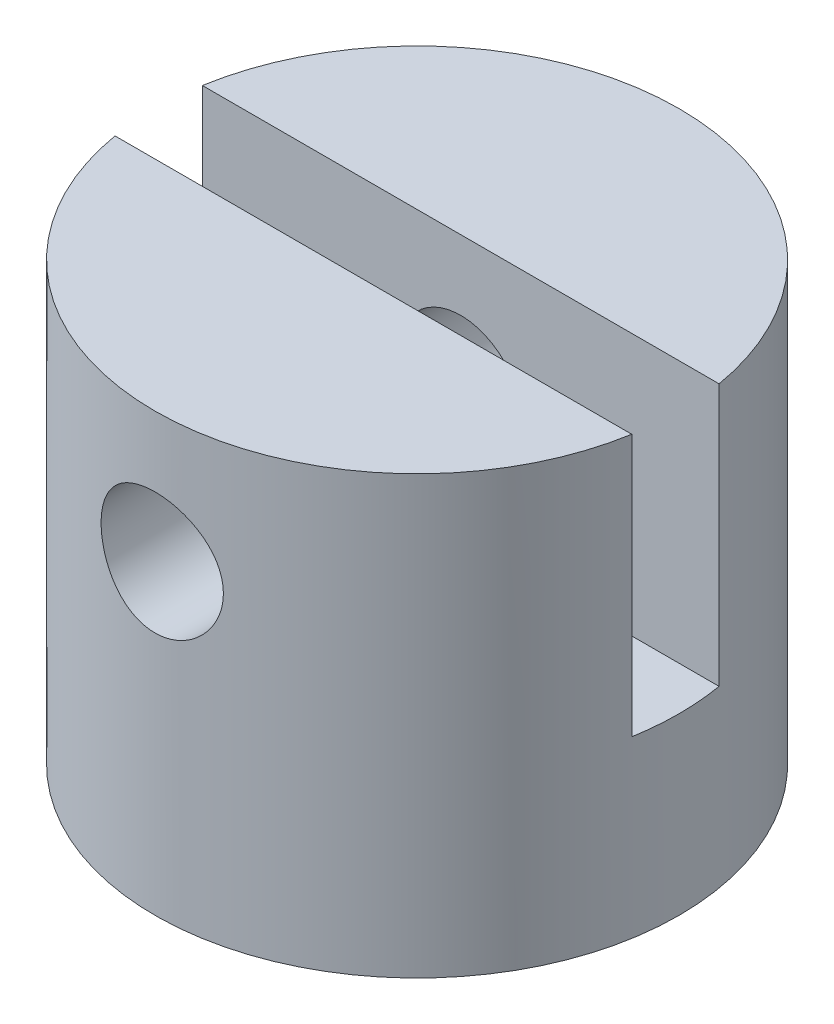
SolidWorks part; units mm, degrees
ref_plane "Front Plane" through (0, 0, 0) normal (0, 0, 1) x (1, 0, 0)
ref_plane "Top Plane" through (0, 0, 0) normal (0, 1, 0) x (1, 0, 0)
ref_plane "Right Plane" through (0, 0, 0) normal (1, 0, 0) x (0, 0, -1)
sketch "Sketch1" plane through (0, 0, 0) normal (0, 0, 1) x (1, 0, 0)
  line L0 (0, -12.5) -> (0, 12.5) construction
  line L5 (0, 12.5) -> (15, 12.5)
  line L6 (15, 12.5) -> (15, -12.5)
  line L7 (15, -12.5) -> (0, -12.5)
  line L8 (0, 12.5) -> (0, -12.5)
  point P1 (-0.2369, 12.5)
  point P3 (0, 0)
  point P5 (15, -12.5)
  point P6 (0, 0)
  point P7 (0, 12.5)
  point P9 (0, 0)
  point P10 (10, 25.837)
  point P12 (15, 0)
  point P13 (0, 12.2278)
  dimension "D1" = 30
  dimension "D2" = 25
revolve "Revolve1" add sketch "Sketch1" angle 360 about L0
sketch "Sketch2" plane through (0, -12.5, 0) normal (0, -1, 0) x (1, 0, 0)
  circle A0 centre (0, 0) radius 5
  dimension "D1" = 10
extrude "Boss-Extrude2" add sketch "Sketch2" along normal blind 5 contours A0
sketch "Sketch4" plane through (0, 0, 0) normal (0, 0, 1) x (1, 0, 0)
  line L1 (-15, -2.5) -> (15, -2.5)
  line L2 (-15, -2.5) -> (-15, 12.5)
  line L3 (-15, 12.5) -> (15, 12.5)
  line L4 (15, -2.5) -> (15, 12.5)
  line L5 (-15, -2.5) -> (15, 12.5) construction
  line L6 (-15, 12.5) -> (15, -2.5) construction
  point P0 (0, 5)
  point P6 (0, 0)
  point P7 (0, 0)
  point P8 (-13.7283, 12.5)
  dimension "D1" = 15
extrude "Cut-Extrude1" cut sketch "Sketch4" against normal mid plane 5
sketch "Sketch5" plane through (0, 0, 0) normal (0, 0, 1) x (1, 0, 0)
  line L1 (14.7902, 12.5) -> (-14.7902, 12.5) construction
  circle A0 centre (0, 5) radius 3.5
  dimension "D1" = 7
  dimension "D2" = 7.5
extrude "Cut-Extrude2" cut sketch "Sketch5" against normal through all both and the other way through all
